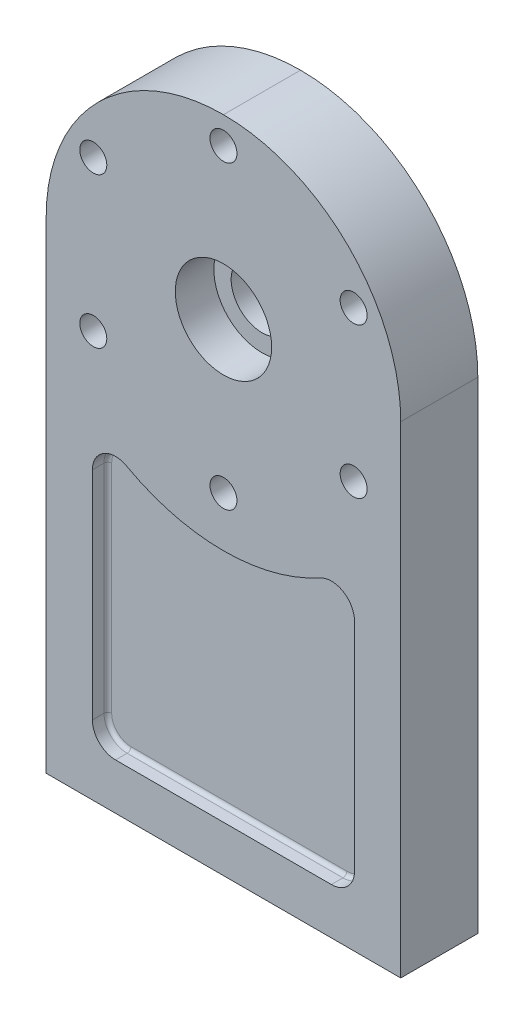
SolidWorks part; units mm, degrees
ref_plane "Front Plane" through (0, 0, 0) normal (0, 0, 1) x (1, 0, 0)
ref_plane "Top Plane" through (0, 0, 0) normal (0, 1, 0) x (1, 0, 0)
ref_plane "Right Plane" through (0, 0, 0) normal (1, 0, 0) x (0, 0, -1)
sketch "Sketch1" plane through (0, 0, 0) normal (0, 0, 1) x (1, 0, 0)
  line L1 (-46, -85.5) -> (46, -85.5)
  line L2 (-46, -85.5) -> (-46, 85.5)
  line L3 (-46, 85.5) -> (46, 85.5)
  line L4 (46, -85.5) -> (46, 85.5)
  line L5 (-46, -85.5) -> (46, 85.5) construction
  line L6 (-46, 85.5) -> (46, -85.5) construction
  point P0 (0, 0)
  dimension "D1" = 92
  dimension "D2" = 171
extrude "Boss-Extrude1" add sketch "Sketch1" along normal mid plane 20
fillet "Fillet1" radius 46 2 edges at (46, 85.5, 0) (-46, 85.5, 0)
sketch "Sketch3" plane through (0, 0, 10) normal (0, 0, 1) x (1, 0, 0)
  line L0 (-46, -85.5) -> (46, -85.5) construction
  circle A0 centre (0, 78.5) radius 3.5
  dimension "D1" = 164
extrude "Cut-Extrude1" cut sketch "Sketch3" against normal through all
sketch "Sketch4" plane through (0, 0, -10) normal (0, 0, -1) x (-1, 0, 0)
  circle A0 centre (0, 78.5) radius 6
extrude "Cut-Extrude2" cut sketch "Sketch4" against normal blind 6
pattern_circular "CirPattern1" count 6 over 360 about axis through (0, 39.5, 10) along (0, 0, 1) of "Cut-Extrude2", "Cut-Extrude1"
sketch "Sketch6" plane through (0, 0, 10) normal (0, 0, 1) x (1, 0, 0)
  line L0 (0, 0) -> (0, 146.9633) construction
  line L1 (-61.0145, 39.5) -> (74.9071, 39.5) construction
  line L2 (-46, -85.5) -> (46, -85.5) construction
  circle A0 centre (0, 39.5) radius 39 construction
  circle A1 centre (0, 39.5) radius 12.5
  dimension "D1" = 125
extrude "Cut-Extrude3" cut sketch "Sketch6" against normal blind 10
sketch "Sketch7" plane through (0, 0, 10) normal (0, 0, 1) x (1, 0, 0)
  circle A0 centre (0, 39.5) radius 8
  dimension "D1" = 16
extrude "Cut-Extrude4" cut sketch "Sketch7" against normal through all
hole_wizard "Tap Drill for M10x1.5 Tap1" positions "Sketch9" profile "Sketch10" hole size "M10x1.5" standard "ANSI Metric"
sketch "Sketch9" plane through (0, -85.5, 0) normal (0, -1, 0) x (-1, 0, 0)
  point P0 (30, 0)
  point P2 (-30, 0)
  dimension "D1" = 30
  dimension "D2" = 60
sketch "Sketch10" plane through (-30, -85.5, 0) normal (1, 0, 0) x (0, 0, -1)
  line L0 (0, 0) -> (0, 10.25)
  line L1 (0, 10.25) -> (4.25, 6)
  line L2 (4.25, 6) -> (4.25, 0)
  line L5 (4.25, 0) -> (0, 0)
  line L10 (0, 10.25) -> (-4.25, 6) construction
  line L11 (0, -6.35) -> (0, 107.95) construction
  dimension "Hole Dia." = 8.5
  dimension "Hole Depth" = 6
  dimension "Drill Angle" = 90
sketch "Sketch12" plane through (0, 0, 10) normal (0, 0, 1) x (1, 0, 0)
  line L11 (34, -73.5) -> (34, 39.5)
  line L12 (-34, -73.5) -> (34, -73.5)
  line L13 (-34, 39.5) -> (-34, -73.5)
  line L14 (34, -67.5) -> (34, -11.2937)
  line L15 (-28, -73.5) -> (28, -73.5)
  line L16 (-34, -11.2937) -> (-34, -67.5)
  arc A0 (-25.1034, -6.0392) -> (25.1034, -6.0392) centre (0, 39.5) ccw
  arc A1 (28, -73.5) -> (34, -67.5) centre (28, -67.5) ccw
  arc A2 (-28, -73.5) -> (-34, -67.5) centre (-28, -67.5) cw
  arc A3 (34, -11.2937) -> (25.1034, -6.0392) centre (28, -11.2937) ccw
  arc A4 (-25.1034, -6.0392) -> (-34, -11.2937) centre (-28, -11.2937) ccw
  dimension "D1" = 12
  dimension "D2" = 104
  dimension "D3" = 6
extrude "Cut-Extrude5" cut sketch "Sketch12" against normal blind 4
mirror "Mirror1" about plane through (0, 0, 0) normal (0, 0, 1) of "Cut-Extrude5"
fillet "Fillet2" radius 1 16 edges at (-31.0513, -6.1275, 6) (0, -12.5, 6) (31.0513, -6.1275, 6) (34, -39.3969, 6) (32.2426, -71.7426, 6) (0, -73.5, 6) (-32.2426, -71.7426, 6) (-34, -39.3969, 6) (31.0513, -6.1275, -6) (34, -39.3969, -6) (32.2426, -71.7426, -6) (0, -73.5, -6) (-32.2426, -71.7426, -6) (-34, -39.3969, -6) (-31.0513, -6.1275, -6) (0, -12.5, -6)
